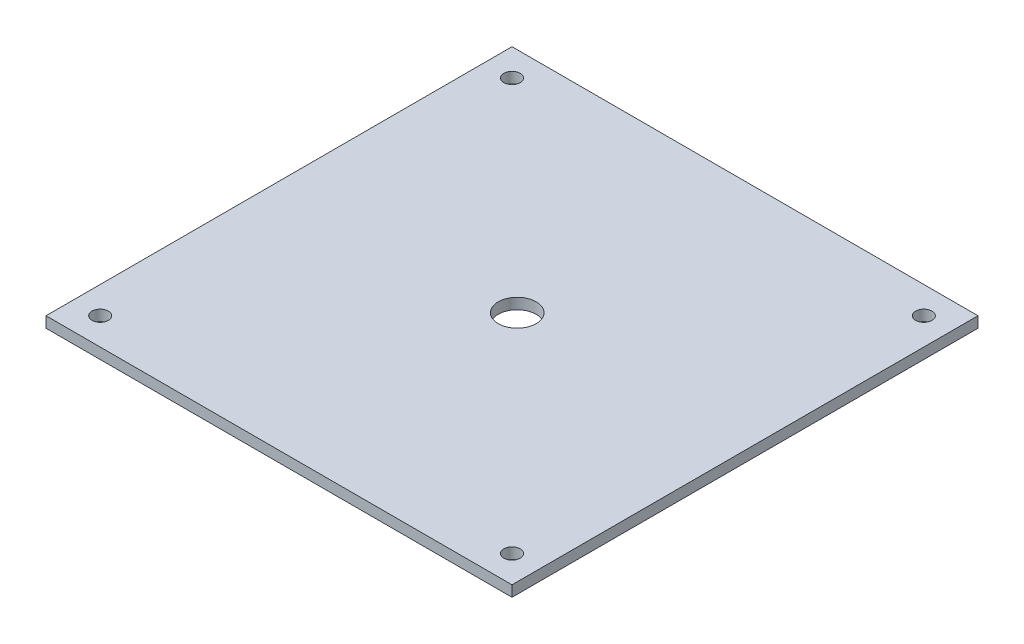
SolidWorks part; units mm, degrees
ref_plane "Front Plane" through (0, 0, 0) normal (0, 0, 1) x (1, 0, 0)
ref_plane "Top Plane" through (0, 0, 0) normal (0, 1, 0) x (1, 0, 0)
ref_plane "Right Plane" through (0, 0, 0) normal (1, 0, 0) x (0, 0, -1)
sketch "Sketch1" plane through (0, 0, 0) normal (0, 1, 0) x (1, 0, 0)
  line L1 (136.525, -136.525) -> (-136.525, -136.525)
  line L2 (136.525, -136.525) -> (136.525, 136.525)
  line L3 (136.525, 136.525) -> (-136.525, 136.525)
  line L4 (-136.525, -136.525) -> (-136.525, 136.525)
  line L5 (136.525, -136.525) -> (-136.525, 136.525) construction
  line L6 (136.525, 136.525) -> (-136.525, -136.525) construction
  circle A0 centre (0, 3.048) radius 11.1125
  point P0 (0, 0)
  dimension "D3" = 3.048
  dimension "D1" = 273.05
  dimension "D2" = 273.05
extrude "Boss-Extrude1" add sketch "Sketch1" along normal blind 6.35
sketch "Sketch2" plane through (0, 6.35, 0) normal (0, 1, 0) x (-1, 0, 0)
  line L0 (0, 136.525) -> (0, -136.525) construction
  line L1 (136.525, 136.525) -> (-136.525, 136.525) construction
  line L2 (-136.525, -136.525) -> (136.525, -136.525) construction
  line L3 (136.525, 0) -> (-136.525, 0) construction
  line L4 (136.525, -136.525) -> (136.525, 136.525) construction
  line L5 (-136.525, 136.525) -> (-136.525, -136.525) construction
  circle A0 centre (120.65, -120.65) radius 4.7625
  circle A1 centre (120.65, 120.65) radius 4.7625
  circle A2 centre (-120.65, -120.65) radius 4.7625
  circle A3 centre (-120.65, 120.65) radius 4.7625
  dimension "D1" = 120.65
extrude "Cut-Extrude1" cut sketch "Sketch2" against normal through all
